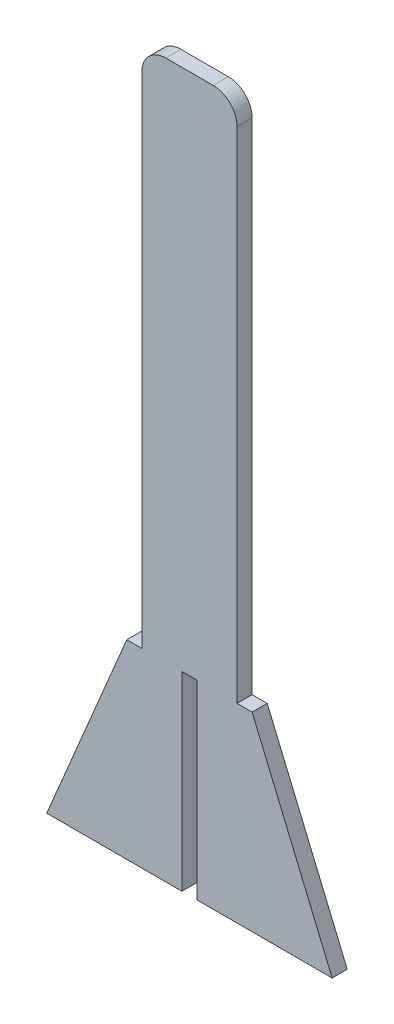
SolidWorks part; units mm, degrees
material "ABS"
ref_plane "Plan de face" through (0, 0, 0) normal (0, 0, 1) x (1, 0, 0)
ref_plane "Plan de dessus" through (0, 0, 0) normal (0, 1, 0) x (1, 0, 0)
ref_plane "Plan de droite" through (0, 0, 0) normal (1, 0, 0) x (0, 0, -1)
sketch "Esquisse1" plane through (0, 0, 0) normal (0, 0, 1) x (1, 0, 0)
  line L1 (-20, 300) -> (20, 300)
  line L2 (-20, 300) -> (-20, 80)
  line L4 (20, 300) -> (20, 80)
  line L8 (-60, 0) -> (60, 0)
  line L9 (26.35, 80) -> (-26.35, 80) construction
  line L10 (26.35, 80) -> (60, 0)
  line L11 (-26.35, 80) -> (-60, 0)
  line L12 (26.35, 80) -> (20, 80)
  line L13 (-20, 80) -> (-26.35, 80)
  point P1 (0, 0)
  point P2 (0, 300)
  point P8 (0, 80)
  dimension "D1" = 80
  dimension "D2" = 120
  dimension "D3" = 40
  dimension "D4" = 300
  dimension "D5" = 6.35
extrude "Boss.-Extru.1" add sketch "Esquisse1" along normal blind 6.35
fillet "Congé1" radius 10 2 edges at (-20, 300, 3.175) (20, 300, 3.175)
sketch "Esquisse2" plane through (0, 0, 6.35) normal (0, 0, 1) x (1, 0, 0)
  line L0 (-60, 0) -> (60, 0) construction
  line L1 (-3.175, 80) -> (3.175, 80)
  line L2 (-3.175, 80) -> (-3.175, 0)
  line L3 (-3.175, 0) -> (3.175, 0)
  line L4 (3.175, 80) -> (3.175, 0)
  line L5 (0, -3.4925) -> (0, 3.4925) construction
  point P8 (0, 80)
  dimension "D1" = 6.35
  dimension "D2" = 80
extrude "Enlèv. mat.-Extru.1" cut sketch "Esquisse2" against normal up to surface (6.35 mm away) up to face at (0, 150.4142, 0)
sketch "Esquisse3" plane through (0, 0, 6.35) normal (0, 0, 1) x (1, 0, 0)
  line L8 (-20, 285) -> (-20, 265)
  line L9 (-20, 265) -> (-13.65, 265)
  line L10 (-13.65, 265) -> (-13.65, 285)
  line L11 (-13.65, 285) -> (-20, 285)
  line L12 (-20, 285) -> (-20, 265)
  line L13 (-20, 265) -> (-13.65, 265)
  line L14 (-13.65, 265) -> (-13.65, 285)
  line L15 (-13.65, 285) -> (-20, 285)
  line L16 (13.65, 285) -> (13.65, 265)
  line L17 (13.65, 265) -> (20, 265)
  line L18 (20, 265) -> (20, 285)
  line L19 (20, 285) -> (13.65, 285)
  line L20 (13.65, 285) -> (13.65, 265)
  line L21 (13.65, 265) -> (20, 265)
  line L22 (20, 265) -> (20, 285)
  line L23 (20, 285) -> (13.65, 285)
  line L24 (-20, 235) -> (-20, 215)
  line L25 (-20, 215) -> (-13.65, 215)
  line L26 (-13.65, 215) -> (-13.65, 235)
  line L27 (-13.65, 235) -> (-20, 235)
  line L28 (-20, 235) -> (-20, 215)
  line L29 (-20, 215) -> (-13.65, 215)
  line L30 (-13.65, 215) -> (-13.65, 235)
  line L31 (-13.65, 235) -> (-20, 235)
  line L32 (13.65, 235) -> (13.65, 215)
  line L33 (13.65, 215) -> (20, 215)
  line L34 (20, 215) -> (20, 235)
  line L35 (20, 235) -> (13.65, 235)
  line L36 (13.65, 235) -> (13.65, 215)
  line L37 (13.65, 215) -> (20, 215)
  line L38 (20, 215) -> (20, 235)
  line L39 (20, 235) -> (13.65, 235)
  dimension "D1" = 0
  dimension "D2" = 0
  dimension "D3" = 0
  dimension "D4" = 0
